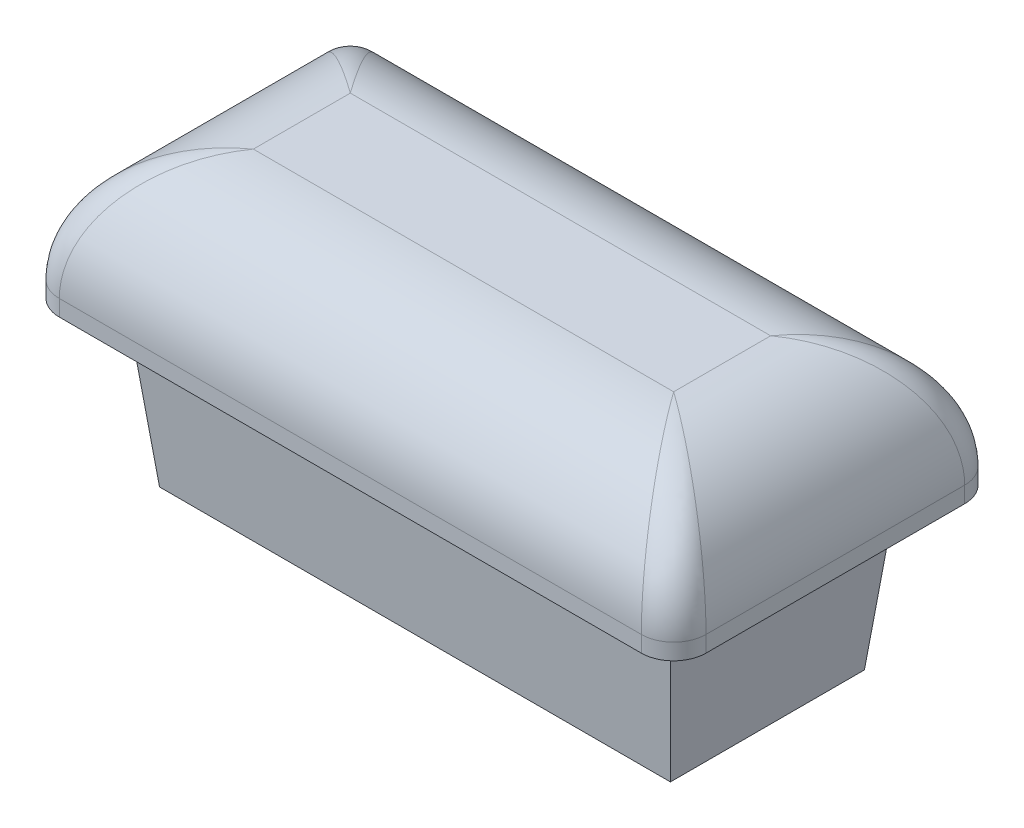
SolidWorks part; units mm, degrees
ref_plane "Front Plane" through (0, 0, 0) normal (0, 0, 1) x (1, 0, 0)
ref_plane "Top Plane" through (0, 0, 0) normal (0, 1, 0) x (1, 0, 0)
ref_plane "Right Plane" through (0, 0, 0) normal (1, 0, 0) x (0, 0, -1)
sketch "Sketch1" plane through (0, 0, 0) normal (0, 1, 0) x (1, 0, 0)
  line L1 (-4.6981, -4.2283) -> (11.9019, -4.2283)
  line L2 (-4.6981, -4.2283) -> (-4.6981, 2.5717)
  line L3 (-4.6981, 2.5717) -> (11.9019, 2.5717)
  line L4 (11.9019, -4.2283) -> (11.9019, 2.5717)
  dimension "D1" = 16.6
  dimension "D2" = 6.8
extrude "Boss-Extrude1" add sketch "Sketch1" along normal blind 5
sketch "Sketch2" plane through (0, 5, 0) normal (0, 1, 0) x (1, 0, 0)
  line L0 (11.9019, 2.5717) -> (-4.6981, -4.2283) construction
  line L1 (-4.6981, 2.5717) -> (11.9019, -4.2283) construction
  line L3 (13.6019, -5.8283) -> (-6.3981, -5.8283)
  line L4 (13.6019, -5.8283) -> (13.6019, 4.1717)
  line L5 (13.6019, 4.1717) -> (-6.3981, 4.1717)
  line L6 (-6.3981, -5.8283) -> (-6.3981, 4.1717)
  line L7 (13.6019, -5.8283) -> (-6.3981, 4.1717) construction
  line L8 (13.6019, 4.1717) -> (-6.3981, -5.8283) construction
  point P8 (3.6019, -0.8283)
  point P9 (3.6019, -0.8283)
  dimension "D1" = 20
  dimension "D2" = 10
extrude "Boss-Extrude2" add sketch "Sketch2" along normal blind 4
fillet "Fillet1" radius 1 4 edges at (-6.3981, 7, -4.1717) (-6.3981, 7, 5.8283) (13.6019, 7, 5.8283) (13.6019, 7, -4.1717)
chamfer "Chamfer1" distance 0.4 angle 84 4 edges at (-4.6981, 0, 0.8283) (3.6019, 0, -2.5717) (11.9019, 0, 0.8283) (3.6019, 0, 4.2283) first distance on face at (3.6019, 0, 0.8283)
fillet "Fillet3" radius 3.5 8 edges at (13.309, 9, -3.8788) (13.6019, 9, 0.8283) (13.309, 9, 5.5354) (3.6019, 9, 5.8283) (-6.1052, 9, 5.5354) (-6.3981, 9, 0.8283) (-6.1052, 9, -3.8788) (3.6019, 9, -4.1717)
